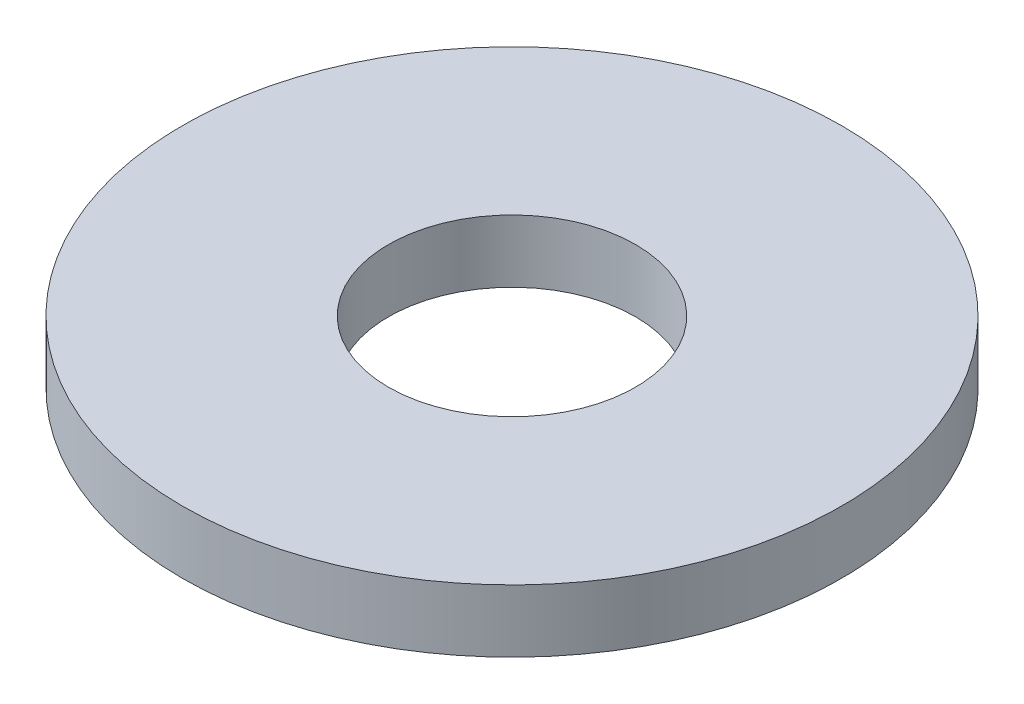
SolidWorks part; units mm, degrees
ref_plane "Front Plane" through (0, 0, 0) normal (0, 0, 1) x (1, 0, 0)
ref_plane "Top Plane" through (0, 0, 0) normal (0, 1, 0) x (1, 0, 0)
ref_plane "Right Plane" through (0, 0, 0) normal (1, 0, 0) x (0, 0, -1)
sketch "Sketch1" plane through (0, 0, 0) normal (0, 1, 0) x (1, 0, 0)
  circle A0 centre (0, 0) radius 100
  dimension "FLANGE_OD" = 200
extrude "Boss-Extrude1" add sketch "Sketch1" along normal blind 19
sketch "Sketch2" plane through (0, 0, 0) normal (0, 1, 0) x (1, 0, 0)
  circle A0 centre (0, 0) radius 37.5
  dimension "BORE_D" = 75
extrude "Cut-Extrude1" cut sketch "Sketch2" along normal through all
sketch "Sketch3" plane through (0, 19, 0) normal (0, 1, 0) x (1, 0, 0)
  circle A0 centre (0, 0) radius 28.1594 construction
  circle A1 centre (-28.1594, 0) radius 7.3235
  dimension "BOLT_D" = 14.6469
  dimension "BOLT_PCD" = 56.3188
extrude "Cut-Extrude2" cut sketch "Sketch3" against normal blind 13.8288 rebuild error yes
pattern_circular "CirPattern1" count 4 over 360 rebuild error yes
